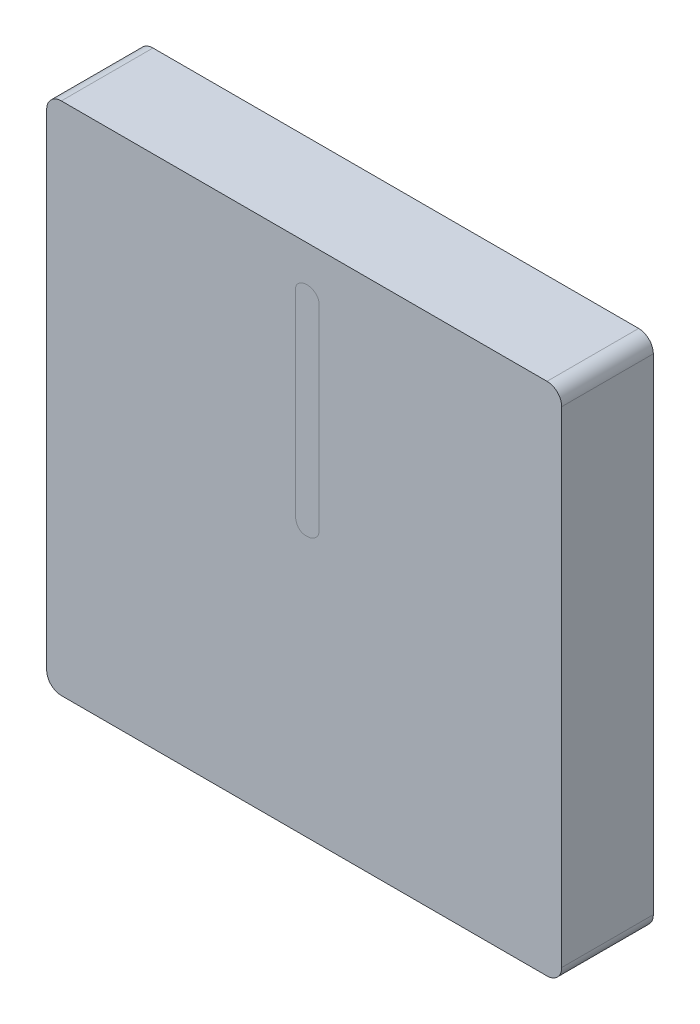
SolidWorks part; units mm, degrees
material "Nylon 101"
ref_plane "Front Plane" through (0, 0, 0) normal (0, 0, 1) x (1, 0, 0)
ref_plane "Top Plane" through (0, 0, 0) normal (0, 1, 0) x (1, 0, 0)
ref_plane "Right Plane" through (0, 0, 0) normal (1, 0, 0) x (0, 0, -1)
sketch "Sketch1" plane through (0, 0, 0) normal (0, 0, 1) x (1, 0, 0)
  line L8 (4.207, 4.461) -> (-4.207, 4.461)
  line L9 (-4.461, 4.207) -> (-4.461, -4.207)
  line L10 (-4.207, -4.461) -> (4.207, -4.461)
  line L11 (4.461, -4.207) -> (4.461, 4.207)
  arc A8 (-4.207, 4.461) -> (-4.461, 4.207) centre (-4.207, 4.207) ccw
  arc A9 (-4.461, -4.207) -> (-4.207, -4.461) centre (-4.207, -4.207) ccw
  arc A10 (4.207, -4.461) -> (4.461, -4.207) centre (4.207, -4.207) ccw
  arc A11 (4.461, 4.207) -> (4.207, 4.461) centre (4.207, 4.207) ccw
  point P0 (0, 0)
  dimension "D3" = 0.254
  dimension "D1" = 8.922
  dimension "D2" = 8.922
  dimension "D4" = 4.461
  dimension "D5" = 4.461
  dimension "D6" = 0.3592
extrude "Boss-Extrude1" add sketch "Sketch1" along normal blind 1.5875
sketch "Sketch2" plane through (0, 0, 1.5875) normal (0, 0, 1) x (1, 0, 0)
  line L0 (4.461, 3.8355) -> (-4.461, 3.8355) construction
  line L1 (4.461, -4.207) -> (4.461, 4.207) construction
  line L2 (-4.461, 4.207) -> (-4.461, -4.207) construction
  text T0 "1" font "GordonURWMed" height in points 16
sketch "Sketch4" plane through (0, 0, 1.5875) normal (0, 0, 1) x (1, 0, 0)
  line L0 (4.461, -0.7785) -> (-4.461, -0.7785) construction
  line L1 (4.461, -4.207) -> (4.461, 4.207) construction
  line L2 (-4.461, 4.207) -> (-4.461, -4.207) construction
  text T0 "N" font "GordonURWMed" height in points 12
wrap "Direction" [suppressed] sketch "Sketch4" source sketch "Sketch4"
split line "Number"
sketch "Sketch5" [suppressed] plane through (0, 0, 1.5875) normal (0, 0, 1) x (1, 0, 0)
  line L0 (4.461, 0) -> (-4.461, 0) construction
  line L1 (4.461, -4.207) -> (4.461, 4.207) construction
  line L2 (-4.461, 4.207) -> (-4.461, -4.207) construction
  line L3 (4.461, 1.651) -> (-4.461, 1.651) construction
  text T0 "CLR" font "GordonURWMed" height in points 14
  dimension "D1" = 1.651
wrap "CLR" [suppressed] sketch "Sketch5" source sketch "Sketch5"
sketch "Sketch6" [suppressed] plane through (0, 0, 1.5875) normal (0, 0, 1) x (1, 0, 0)
  line L0 (4.461, 0) -> (-4.461, 0) construction
  line L4 (4.461, 1.651) -> (-4.461, 1.651) construction
  text T0 "ENT" font "GordonURWCon" height in points 16
  dimension "D1" = 1.651
wrap "ENT" [suppressed] sketch "Sketch6" source sketch "Sketch6"
sketch "Sketch8" plane through (0, 0, 1.5875) normal (0, 0, 1) x (1, 0, 0)
  line L0 (4.461, 3.302) -> (-4.461, 3.302) construction
  line L3 (4.461, 0) -> (-4.461, 0) construction
  line L4 (4.461, -0.508) -> (-4.461, -0.508) construction
  text T0 "EM" font "GordonURWCon" height in points 14
  text T1 "CON" font "GordonURWCon" height in points 14
  point P13 (0, 0)
  dimension "D1" = 3.302
  dimension "D2" = 0.508
wrap "EMCON" [suppressed] sketch "Sketch8" source sketch "Sketch8"
sketch "Sketch9" [suppressed] plane through (0, 0, 0) normal (0, 0, 1) x (1, 0, 0)
  line L0 (4.461, 3.302) -> (-4.461, 3.302) construction
  line L3 (4.461, 0) -> (-4.461, 0) construction
  line L4 (4.461, -0.508) -> (-4.461, -0.508) construction
  text T0 "ON" font "GordonURWCon" height in points 14
  text T1 "OFF" font "GordonURWCon" height in points 14
  point P13 (0, 0)
  dimension "D1" = 3.302
  dimension "D2" = 0.508
wrap "ON-OFF" [suppressed] sketch "Sketch9" source sketch "Sketch9" thickness 0.0762 parameters "D1"=0.0762
sketch "Sketch10" [suppressed] plane through (0, 0, 0) normal (0, 0, 1) x (1, 0, 0)
  line L0 (4.461, 0) -> (-4.461, 0) construction
  line L4 (4.461, 1.651) -> (-4.461, 1.651) construction
  text T0 "IFF" font "GordonURWCon" height in points 16
  dimension "D1" = 1.651
wrap "LEGEND" [suppressed] sketch "Sketch10" source sketch "Sketch10" thickness 0.0762 parameters "D1"=0.0762
sketch "Sketch11" [suppressed] plane through (0, 0, 1.5875) normal (0, 0, 1) x (1, 0, 0)
  spline S0 degree 3 poles (0.4333, 2.1341) (0.15, 2.1032) (-0.1198, 2.088) (-0.4121, 2.1993) (-0.5959, 2.4579) (-0.6685, 2.7897) (-0.5423, 3.1163) (-0.3233, 3.3286) (-0.0755, 3.3609) (0.1283, 3.3738) (0.3391, 3.3596) (0.5236, 3.2792) (0.6786, 3.1258) (0.7786, 2.9088) (0.8035, 2.6123) (0.682, 2.313) (0.4333, 2.1341) (0.15, 2.1032) (-0.1198, 2.088) knots -0.201217 -0.119698 -0.046549 0 0.077824 0.141317 0.20865 0.291476 0.367822 0.445307 0.489891 0.538926 0.589041 0.636005 0.676198 0.739165 0.798783 0.880302 0.953451 1 1.077824 1.141317 1.20865 only from (0.1949, 2.1094) to (0.1949, 2.1094)
split line "Split Line1" [suppressed]
